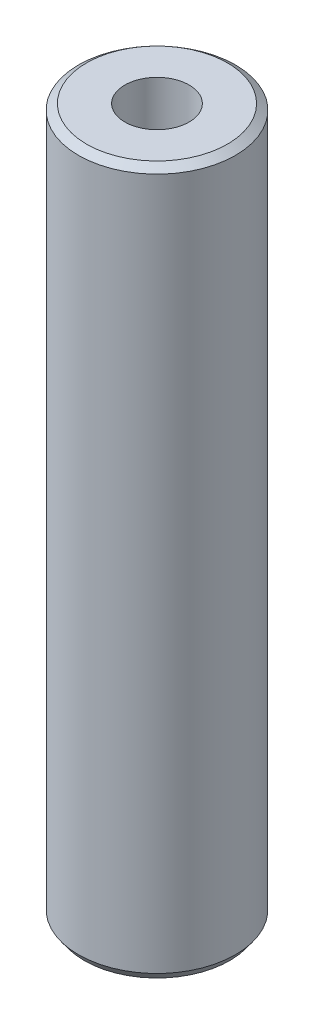
SolidWorks part; units mm, degrees
ref_plane "Front Plane" through (0, 0, 0) normal (0, 0, 1) x (1, 0, 0)
ref_plane "Top Plane" through (0, 0, 0) normal (0, 1, 0) x (1, 0, 0)
ref_plane "Right Plane" through (0, 0, 0) normal (1, 0, 0) x (0, 0, -1)
sketch "Sketch1" plane through (0, 0, 0) normal (0, 1, 0) x (1, 0, 0)
  circle A0 centre (0, 0) radius 12.5
  dimension "SHAFT_OD" = 25
extrude "Boss-Extrude1" add sketch "Sketch1" along normal blind 112.5047
sketch "Sketch2" plane through (0, 0, 0) normal (0, 1, 0) x (1, 0, 0)
  circle A0 centre (0, 0) radius 5.1191
  dimension "BORE_D" = 10.2381
extrude "Cut-Extrude1" cut sketch "Sketch2" along normal through all
chamfer "Chamfer1" distance 0.9137 angle 54.341 2 edges at (0, 112.5047, 12.5) (0, 0, 12.5) first distance on face at (0, 112.5047, 12.5) first distance on face at (0, 0, 5.1191)
